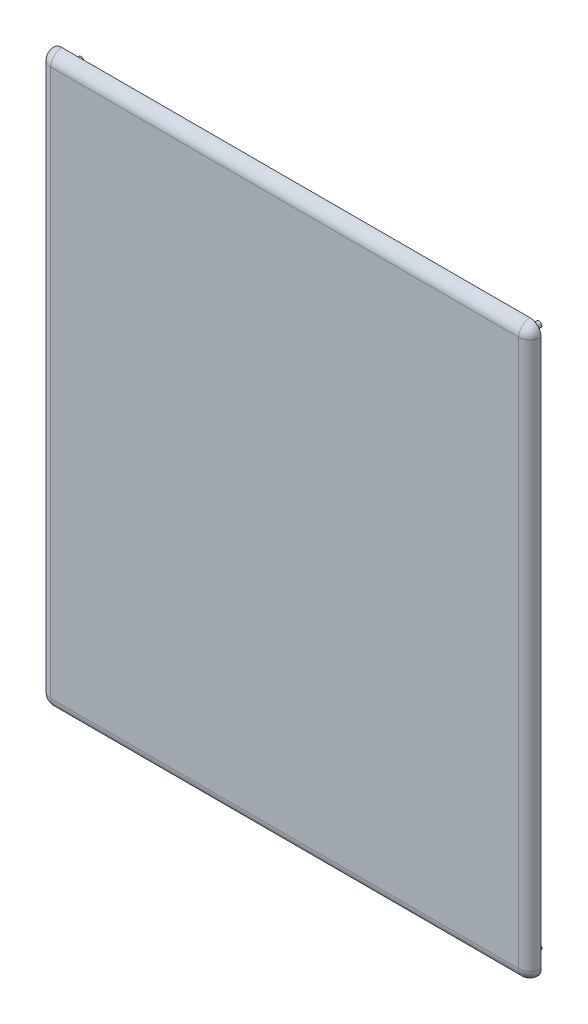
SolidWorks part; units mm, degrees
ref_plane "Front Plane" through (0, 0, 0) normal (0, 0, 1) x (1, 0, 0)
ref_plane "Top Plane" through (0, 0, 0) normal (0, 1, 0) x (1, 0, 0)
ref_plane "Right Plane" through (0, 0, 0) normal (1, 0, 0) x (0, 0, -1)
sketch "Sketch1" plane through (0, 0, 0) normal (0, 0, 1) x (1, 0, 0)
  line L1 (0, 0) -> (220.98, 0)
  line L2 (0, 0) -> (0, 256.54)
  line L3 (0, 256.54) -> (220.98, 256.54)
  line L4 (220.98, 0) -> (220.98, 256.54)
  dimension "D1" = 256.54
  dimension "D2" = 220.98
extrude "Boss-Extrude1" add sketch "Sketch1" along normal blind 5.08
fillet "Fillet1" radius 5.08 4 edges at (110.49, 0, 5.08) (220.98, 128.27, 5.08) (0, 128.27, 5.08) (110.49, 256.54, 5.08)
fillet "Fillet2" radius 5.08 4 edges at (1.4879, 1.4879, 3.5921) (219.4921, 1.4879, 3.5921) (219.4921, 255.0521, 3.5921) (1.4879, 255.0521, 3.5921)
sketch "Sketch2" plane through (0, 0, 0) normal (0, 0, -1) x (-1, 0, 0)
  line L0 (-110.49, 6.7945) -> (-110.49, 0) construction
  line L1 (-5.08, 0) -> (-215.9, 0) construction
  line L2 (-213.6775, 128.27) -> (-220.98, 128.27) construction
  line L3 (-220.98, 5.08) -> (-220.98, 251.46) construction
  line L4 (-7.3025, 128.27) -> (0, 128.27) construction
  line L5 (0, 251.46) -> (0, 5.08) construction
  line L6 (-220.98, 223.2189) -> (0, 223.2189) construction
  line L7 (-140.5516, 256.54) -> (-140.5516, 0) construction
  line L10 (-110.49, 249.7455) -> (-110.49, 256.54) construction
  line L11 (-213.6775, 249.7455) -> (-7.3025, 249.7455) construction
  line L12 (-213.6775, 249.7455) -> (-213.6775, 6.7945) construction
  line L13 (-213.6775, 6.7945) -> (-7.3025, 6.7945) construction
  line L14 (-7.3025, 249.7455) -> (-7.3025, 6.7945) construction
  line L15 (-215.9, 256.54) -> (-5.08, 256.54) construction
  circle A0 centre (-213.6775, 249.7455) radius 1.27
  circle A1 centre (-7.3025, 249.7455) radius 1.27
  circle A2 centre (-213.6775, 6.7945) radius 1.27
  circle A3 centre (-7.3025, 6.7945) radius 1.27
  dimension "D3" = 2.54
  dimension "D1" = 7.3025
  dimension "D2" = 6.7945
  dimension "D4" = 220.98
  dimension "D5" = 7.3025
  dimension "D6" = 256.54
extrude "Boss-Extrude2" add sketch "Sketch2" along normal blind 6.35
